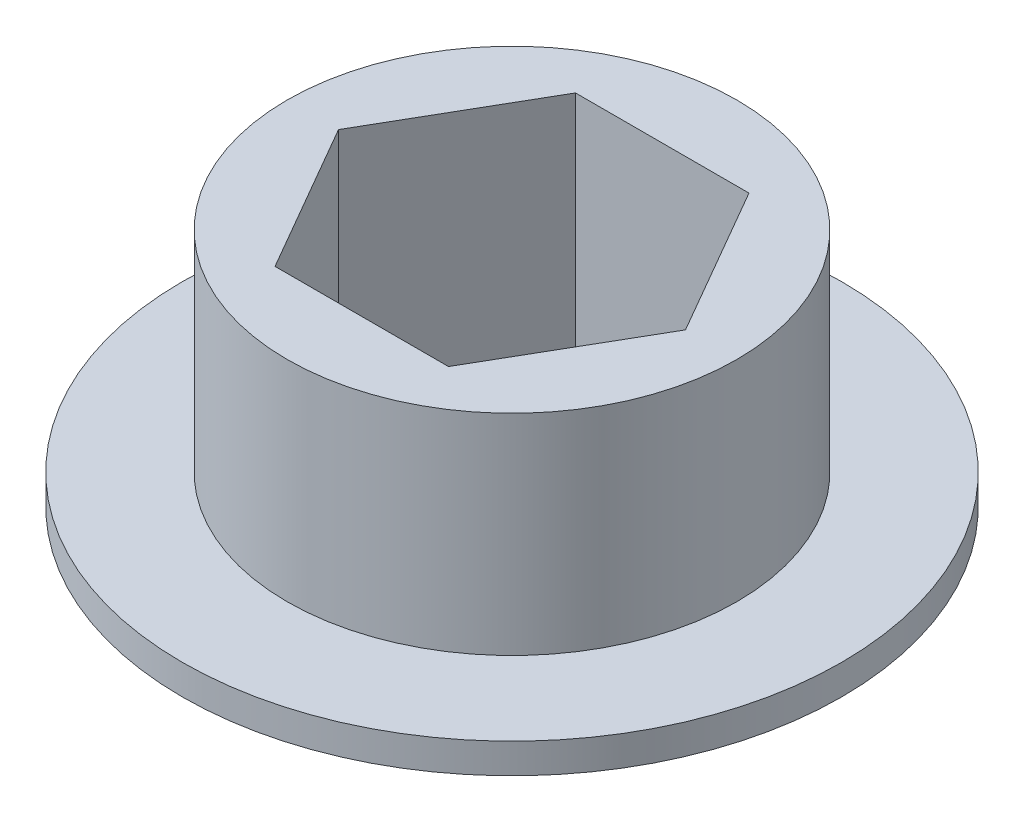
SolidWorks part; units mm, degrees
ref_plane "Front Plane" through (0, 0, 0) normal (0, 0, 1) x (1, 0, 0)
ref_plane "Top Plane" through (0, 0, 0) normal (0, 1, 0) x (1, 0, 0)
ref_plane "Right Plane" through (0, 0, 0) normal (1, 0, 0) x (0, 0, -1)
sketch "Sketch1" plane through (0, 0, 0) normal (0, 1, 0) x (1, 0, 0)
  line L0 (-2.894, -5.0125) -> (2.894, -5.0125)
  line L1 (2.894, -5.0125) -> (5.7879, 0)
  line L2 (5.7879, 0) -> (2.894, 5.0125)
  line L3 (2.894, 5.0125) -> (-2.894, 5.0125)
  line L4 (-2.894, 5.0125) -> (-5.7879, 0)
  line L5 (-5.7879, 0) -> (-2.894, -5.0125)
  circle A0 centre (0, 0) radius 7.5
  point P7 (0, 0)
  point P9 (0, 5.0125)
  dimension "D3" = 15
  dimension "D1" = 120
  dimension "D2" = 10.025
extrude "Boss-Extrude1" add sketch "Sketch1" along normal mid plane 8
ref_axis "Axis1" through (0, 0, 0) along (0, 1, 0)
sketch "Sketch2" plane through (0, -4, 0) normal (0, -1, 0) x (1, 0, 0)
  circle A0 centre (0, 0) radius 11
  circle A1 centre (0, 0) radius 7.5
  circle A2 centre (0, 0) radius 7.5 construction
  dimension "D1" = 3.5
extrude "Boss-Extrude2" add sketch "Sketch2" against normal blind 1
